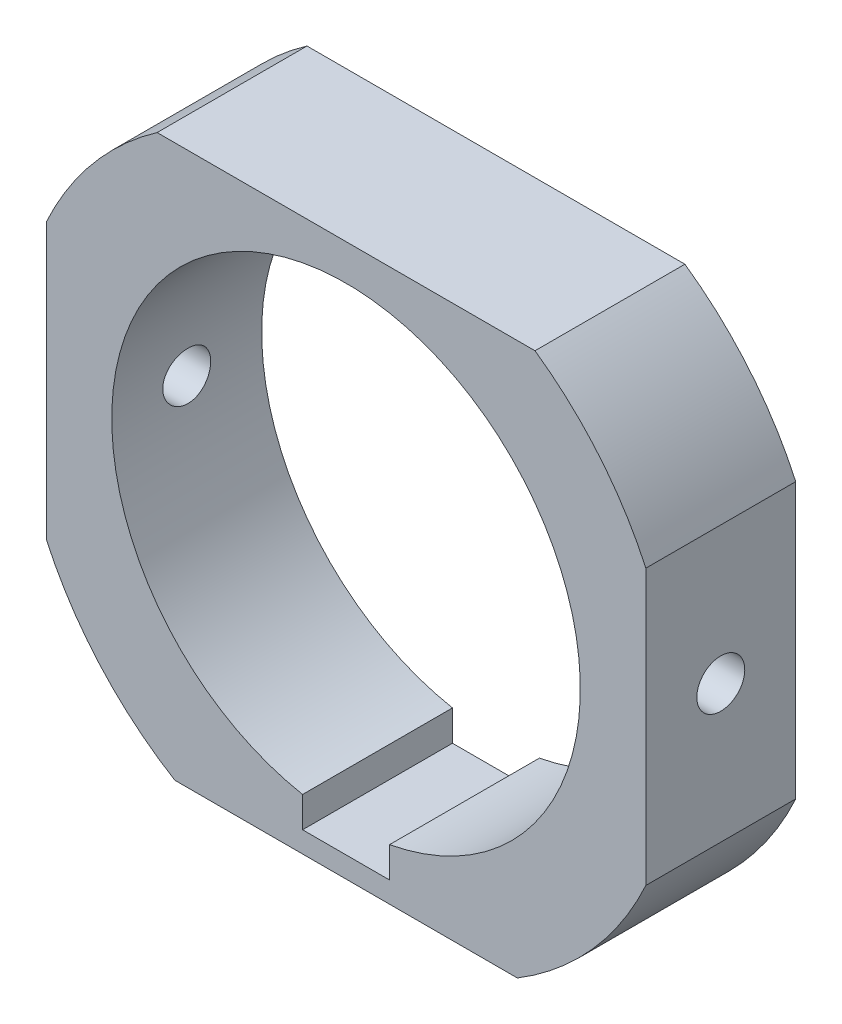
SolidWorks part; units mm, degrees
ref_plane "Front Plane" through (0, 0, 0) normal (0, 0, 1) x (1, 0, 0)
ref_plane "Top Plane" through (0, 0, 0) normal (0, 1, 0) x (1, 0, 0)
ref_plane "Right Plane" through (0, 0, 0) normal (1, 0, 0) x (0, 0, -1)
sketch "Sketch1" plane through (0, 0, 0) normal (0, 0, 1) x (1, 0, 0)
  line L1 (-6.3032, 9.015) -> (6.3032, 9.015)
  line L2 (11, 0) -> (-11, 0) construction
  line L3 (-4.7948, -9.9) -> (4.7948, -9.9)
  line L5 (10, 4.5826) -> (10, -4.5826)
  line L7 (0, 11) -> (0, -11) construction
  line L8 (-10, 4.5826) -> (-10, -4.5826)
  line L9 (-1.25, -8.5) -> (1.25, -8.5)
  line L10 (1.25, -8.5) -> (1.25, -7.5117)
  line L11 (-1.25, -8.5) -> (-1.25, -7.7144)
  line L13 (1.45, -8.7) -> (1.45, -7.4757)
  line L14 (-1.45, -8.7) -> (1.45, -8.7)
  line L15 (-1.45, -8.7) -> (-1.45, -7.6793)
  line L16 (-1.45, -8.7) -> (-1.45, -7.7144) construction
  line L17 (1.45, -8.7) -> (1.45, -7.5117) construction
  circle A0 centre (0, 0) radius 7.815
  circle A2 centre (0, 0) radius 7.815
  circle A3 centre (0, 0) radius 11
  dimension "D2" = 1.2
  dimension "D4" = 1.2
  dimension "D1" = 0
  dimension "D3" = 0.2
extrude "Boss-Extrude1" add sketch "Sketch1" along normal blind 5 contours L5 A3 L1 L8 A2 region at (0, 8.7397, 0)
sketch "Sketch2" plane through (0, 0, 0) normal (1, 0, 0) x (0, 0, -1)
  line L0 (-5, -4.5826) -> (-5, -9.9) construction
  line L1 (0, -9.9) -> (-5, -9.9)
  line L3 (0, -9.9) -> (0, -9.4)
  line L5 (0, -9.4) -> (-5, -9.4)
  line L6 (-5, -9.9) -> (-5, -9.4)
  line L7 (0, -9.9) -> (-5, -9.4) construction
  line L8 (0, -9.4) -> (-5, -9.9) construction
  point P4 (-2.5, -9.65)
  dimension "D1" = 0.5
extrude "Cut-Extrude1" cut sketch "Sketch2" against normal through all and the other way through all
sketch "Sketch3" plane through (10, 0, 0) normal (1, 0, 0) x (0, 0, -1)
  line L0 (-2.5, 4.5826) -> (-2.5, -4.5826) construction
  line L1 (-5, 4.5826) -> (0, 4.5826) construction
  line L2 (-5, -4.5826) -> (0, -4.5826) construction
  line L3 (-5, 0) -> (0, 0) construction
  line L4 (-5, 4.5826) -> (-5, -4.5826) construction
  circle A0 centre (-2.5, 0) radius 0.8
  dimension "D1" = 1.6
extrude "Cut-Extrude2" cut sketch "Sketch3" against normal through all
